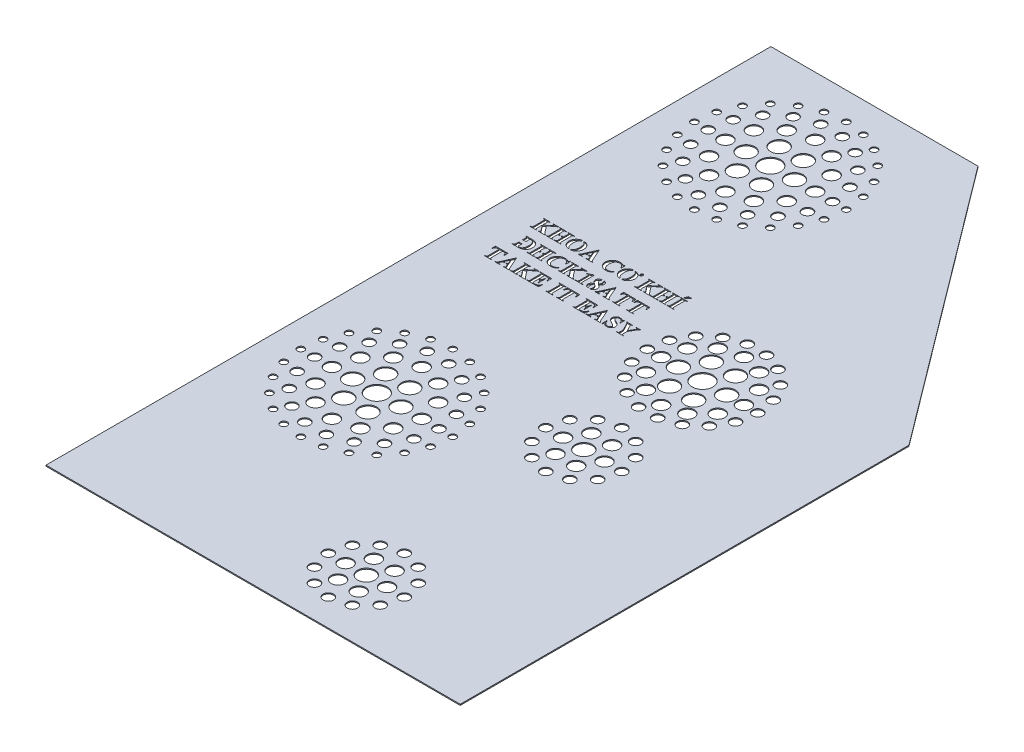
SolidWorks part; units mm, degrees
ref_plane "Front Plane" through (0, 0, 0) normal (0, 0, 1) x (1, 0, 0)
ref_plane "Top Plane" through (0, 0, 0) normal (0, 1, 0) x (1, 0, 0)
ref_plane "Right Plane" through (0, 0, 0) normal (1, 0, 0) x (0, 0, -1)
sketch "Sketch1" plane through (0, 0, 0) normal (0, 1, 0) x (1, 0, 0)
  line L0 (286.5, 0) -> (-313.5, 0)
  line L1 (-313.5, 0) -> (-313.5, 1050)
  line L2 (-313.5, 1050) -> (-13.5, 1050)
  line L3 (-13.5, 1050) -> (286.5, 650)
  line L4 (286.5, 650) -> (286.5, 0)
  line L5 (-263.5, 650) -> (-63.5, 650) construction
  circle A259 centre (91.5, 581) radius 12.5
  circle A260 centre (116.5, 581) radius 10
  circle A261 centre (136.5, 581) radius 7.5
  circle A263 centre (56.5, 581) radius 15
  circle A264 centre (74, 550.6891) radius 12.5
  circle A265 centre (39, 550.6891) radius 12.5
  circle A266 centre (21.5, 581) radius 12.5
  circle A267 centre (39, 611.3109) radius 12.5
  circle A268 centre (74, 611.3109) radius 12.5
  circle A269 centre (108.4615, 551) radius 10
  circle A270 centre (86.5, 529.0385) radius 10
  circle A271 centre (56.5, 521) radius 10
  circle A272 centre (26.5, 529.0385) radius 10
  circle A273 centre (4.5385, 551) radius 10
  circle A274 centre (-3.5, 581) radius 10
  circle A275 centre (4.5385, 611) radius 10
  circle A276 centre (26.5, 632.9615) radius 10
  circle A277 centre (56.5, 641) radius 10
  circle A278 centre (86.5, 632.9615) radius 10
  circle A279 centre (108.4615, 611) radius 10
  circle A280 centre (131.6754, 553.6384) radius 7.5
  circle A281 centre (117.7836, 529.577) radius 7.5
  circle A282 centre (96.5, 511.718) radius 7.5
  circle A283 centre (70.3919, 502.2154) radius 7.5
  circle A284 centre (42.6081, 502.2154) radius 7.5
  circle A285 centre (16.5, 511.718) radius 7.5
  circle A286 centre (-4.7836, 529.577) radius 7.5
  circle A287 centre (-18.6754, 553.6384) radius 7.5
  circle A288 centre (-23.5, 581) radius 7.5
  circle A289 centre (-18.6754, 608.3616) radius 7.5
  circle A290 centre (-4.7836, 632.423) radius 7.5
  circle A291 centre (16.5, 650.282) radius 7.5
  circle A292 centre (42.6081, 659.7846) radius 7.5
  circle A293 centre (70.3919, 659.7846) radius 7.5
  circle A294 centre (96.5, 650.282) radius 7.5
  circle A295 centre (117.7836, 632.423) radius 7.5
  circle A296 centre (131.6754, 608.3616) radius 7.5
  circle A362 centre (86.5, 409) radius 10
  circle A363 centre (111.5, 409) radius 7.5
  circle A364 centre (71.5, 383.0192) radius 10
  circle A365 centre (41.5, 383.0192) radius 10
  circle A366 centre (26.5, 409) radius 10
  circle A367 centre (41.5, 434.9808) radius 10
  circle A368 centre (71.5, 434.9808) radius 10
  circle A369 centre (104.1314, 381.5) radius 7.5
  circle A370 centre (84, 361.3686) radius 7.5
  circle A371 centre (56.5, 354) radius 7.5
  circle A372 centre (29, 361.3686) radius 7.5
  circle A373 centre (8.8686, 381.5) radius 7.5
  circle A374 centre (1.5, 409) radius 7.5
  circle A375 centre (8.8686, 436.5) radius 7.5
  circle A376 centre (29, 456.6314) radius 7.5
  circle A377 centre (56.5, 464) radius 7.5
  circle A378 centre (84, 456.6314) radius 7.5
  circle A379 centre (104.1314, 436.5) radius 7.5
  circle A380 centre (56.5, 409) radius 12.5
  circle A381 centre (86.5, 94) radius 10
  circle A382 centre (111.5, 94) radius 7.5
  circle A383 centre (71.5, 68.0192) radius 10
  circle A384 centre (41.5, 68.0192) radius 10
  circle A385 centre (26.5, 94) radius 10
  circle A386 centre (41.5, 119.9808) radius 10
  circle A387 centre (71.5, 119.9808) radius 10
  circle A388 centre (104.1314, 66.5) radius 7.5
  circle A389 centre (84, 46.3686) radius 7.5
  circle A390 centre (56.5, 39) radius 7.5
  circle A391 centre (29, 46.3686) radius 7.5
  circle A392 centre (8.8686, 66.5) radius 7.5
  circle A393 centre (1.5, 94) radius 7.5
  circle A394 centre (8.8686, 121.5) radius 7.5
  circle A395 centre (29, 141.6314) radius 7.5
  circle A396 centre (56.5, 149) radius 7.5
  circle A397 centre (84, 141.6314) radius 7.5
  circle A398 centre (104.1314, 121.5) radius 7.5
  circle A399 centre (56.5, 94) radius 12.5
  circle A400 centre (-164.5, 330.2) radius 15
  circle A401 centre (-129.5, 330.2) radius 12.5
  circle A402 centre (-99.5, 330.2) radius 10
  circle A403 centre (-74.5, 330.2) radius 7.5
  circle A404 centre (-54.5, 330.2) radius 5
  circle A407 centre (-147, 299.8891) radius 12.5
  circle A408 centre (-182, 299.8891) radius 12.5
  circle A409 centre (-199.5, 330.2) radius 12.5
  circle A410 centre (-182, 360.5109) radius 12.5
  circle A411 centre (-147, 360.5109) radius 12.5
  circle A412 centre (-108.2083, 297.7) radius 10
  circle A413 centre (-132, 273.9083) radius 10
  circle A414 centre (-164.5, 265.2) radius 10
  circle A415 centre (-197, 273.9083) radius 10
  circle A416 centre (-220.7917, 297.7) radius 10
  circle A417 centre (-229.5, 330.2) radius 10
  circle A418 centre (-220.7917, 362.7) radius 10
  circle A419 centre (-197, 386.4917) radius 10
  circle A420 centre (-164.5, 395.2) radius 10
  circle A421 centre (-132, 386.4917) radius 10
  circle A422 centre (-108.2083, 362.7) radius 10
  circle A423 centre (-79.9277, 299.4182) radius 7.5
  circle A424 centre (-95.556, 272.3491) radius 7.5
  circle A425 centre (-119.5, 252.2577) radius 7.5
  circle A426 centre (-148.8717, 241.5673) radius 7.5
  circle A427 centre (-180.1283, 241.5673) radius 7.5
  circle A428 centre (-209.5, 252.2577) radius 7.5
  circle A429 centre (-233.444, 272.3491) radius 7.5
  circle A430 centre (-249.0723, 299.4182) radius 7.5
  circle A431 centre (-254.5, 330.2) radius 7.5
  circle A432 centre (-249.0723, 360.9818) radius 7.5
  circle A433 centre (-233.444, 388.0509) radius 7.5
  circle A434 centre (-209.5, 408.1423) radius 7.5
  circle A435 centre (-180.1283, 418.8327) radius 7.5
  circle A436 centre (-148.8717, 418.8327) radius 7.5
  circle A437 centre (-119.5, 408.1423) radius 7.5
  circle A438 centre (-95.556, 388.0509) radius 7.5
  circle A439 centre (-79.9277, 360.9818) radius 7.5
  circle A440 centre (-58.2482, 301.7299) radius 5
  circle A441 centre (-69.2372, 275.2) radius 5
  circle A442 centre (-86.7183, 252.4183) radius 5
  circle A443 centre (-109.5, 234.9372) radius 5
  circle A444 centre (-136.0299, 223.9482) radius 5
  circle A445 centre (-164.5, 220.2) radius 5
  circle A446 centre (-192.9701, 223.9482) radius 5
  circle A447 centre (-219.5, 234.9372) radius 5
  circle A448 centre (-242.2817, 252.4183) radius 5
  circle A449 centre (-259.7628, 275.2) radius 5
  circle A450 centre (-270.7518, 301.7299) radius 5
  circle A451 centre (-274.5, 330.2) radius 5
  circle A452 centre (-270.7518, 358.6701) radius 5
  circle A453 centre (-259.7628, 385.2) radius 5
  circle A454 centre (-242.2817, 407.9817) radius 5
  circle A455 centre (-219.5, 425.4628) radius 5
  circle A456 centre (-192.9701, 436.4518) radius 5
  circle A457 centre (-164.5, 440.2) radius 5
  circle A458 centre (-136.0299, 436.4518) radius 5
  circle A459 centre (-109.5, 425.4628) radius 5
  circle A460 centre (-86.7183, 407.9817) radius 5
  circle A461 centre (-69.2372, 385.2) radius 5
  circle A462 centre (-58.2482, 358.6701) radius 5
  circle A463 centre (-164.5, 900.2) radius 15
  circle A464 centre (-129.5, 900.2) radius 12.5
  circle A465 centre (-99.5, 900.2) radius 10
  circle A466 centre (-74.5, 900.2) radius 7.5
  circle A467 centre (-54.5, 900.2) radius 5
  circle A468 centre (-147, 869.8891) radius 12.5
  circle A469 centre (-182, 869.8891) radius 12.5
  circle A470 centre (-199.5, 900.2) radius 12.5
  circle A471 centre (-182, 930.5109) radius 12.5
  circle A472 centre (-147, 930.5109) radius 12.5
  circle A473 centre (-108.2083, 867.7) radius 10
  circle A474 centre (-132, 843.9083) radius 10
  circle A475 centre (-164.5, 835.2) radius 10
  circle A476 centre (-197, 843.9083) radius 10
  circle A477 centre (-220.7917, 867.7) radius 10
  circle A478 centre (-229.5, 900.2) radius 10
  circle A479 centre (-220.7917, 932.7) radius 10
  circle A480 centre (-197, 956.4917) radius 10
  circle A481 centre (-164.5, 965.2) radius 10
  circle A482 centre (-132, 956.4917) radius 10
  circle A483 centre (-108.2083, 932.7) radius 10
  circle A484 centre (-79.9277, 869.4182) radius 7.5
  circle A485 centre (-95.556, 842.3491) radius 7.5
  circle A486 centre (-119.5, 822.2577) radius 7.5
  circle A487 centre (-148.8717, 811.5673) radius 7.5
  circle A488 centre (-180.1283, 811.5673) radius 7.5
  circle A489 centre (-209.5, 822.2577) radius 7.5
  circle A490 centre (-233.444, 842.3491) radius 7.5
  circle A491 centre (-249.0723, 869.4182) radius 7.5
  circle A492 centre (-254.5, 900.2) radius 7.5
  circle A493 centre (-249.0723, 930.9818) radius 7.5
  circle A494 centre (-233.444, 958.0509) radius 7.5
  circle A495 centre (-209.5, 978.1423) radius 7.5
  circle A496 centre (-180.1283, 988.8327) radius 7.5
  circle A497 centre (-148.8717, 988.8327) radius 7.5
  circle A498 centre (-119.5, 978.1423) radius 7.5
  circle A499 centre (-95.556, 958.0509) radius 7.5
  circle A500 centre (-79.9277, 930.9818) radius 7.5
  circle A501 centre (-58.2482, 871.7299) radius 5
  circle A502 centre (-69.2372, 845.2) radius 5
  circle A503 centre (-86.7183, 822.4183) radius 5
  circle A504 centre (-109.5, 804.9372) radius 5
  circle A505 centre (-136.0299, 793.9482) radius 5
  circle A506 centre (-164.5, 790.2) radius 5
  circle A507 centre (-192.9701, 793.9482) radius 5
  circle A508 centre (-219.5, 804.9372) radius 5
  circle A509 centre (-242.2817, 822.4183) radius 5
  circle A510 centre (-259.7628, 845.2) radius 5
  circle A511 centre (-270.7518, 871.7299) radius 5
  circle A512 centre (-274.5, 900.2) radius 5
  circle A513 centre (-270.7518, 928.6701) radius 5
  circle A514 centre (-259.7628, 955.2) radius 5
  circle A515 centre (-242.2817, 977.9817) radius 5
  circle A516 centre (-219.5, 995.4628) radius 5
  circle A517 centre (-192.9701, 1006.4518) radius 5
  circle A518 centre (-164.5, 1010.2) radius 5
  circle A519 centre (-136.0299, 1006.4518) radius 5
  circle A520 centre (-109.5, 995.4628) radius 5
  circle A521 centre (-86.7183, 977.9817) radius 5
  circle A522 centre (-69.2372, 955.2) radius 5
  circle A523 centre (-58.2482, 928.6701) radius 5
  text T0 "<b>KHOA CƠ KHÍ</b>\r\n<b>DHCK18ATT</b>\r\n<b>TAKE IT EASY</b>" font "Times New Roman" height 20
  point P32 (-164.5, 330.2)
  point P56 (-164.5, 330.2)
  point P90 (-164.5, 330.2)
  point P137 (-164.5, 330.2)
  point P156 (-164.5, 900.2)
  point P180 (-164.5, 900.2)
  point P214 (-164.5, 900.2)
  point P261 (-164.5, 900.2)
  point P550 (56.5, 581)
  point P574 (56.5, 581)
  point P609 (56.5, 581)
  point P656 (56.5, 581)
  point P672 (56.5, 409)
  point P695 (56.5, 409)
  point P710 (56.5, 94)
  point P733 (56.5, 94)
  dimension "D5" = 30
  dimension "D6" = 35
  dimension "D7" = 2
  dimension "D8" = 2
  dimension "D16" = 172
  dimension "D9" = 35
  dimension "D17" = 30
  dimension "D18" = 6
  dimension "D10" = 30
  dimension "D11" = 25
  dimension "D12" = 20
  dimension "D13" = 25
  dimension "D14" = 20
  dimension "D15" = 15
  dimension "D27" = 10
  dimension "D29" = 719.8
  dimension "D30" = 25
  dimension "D31" = 20
  dimension "D32" = 20
  dimension "D21" = 25
  dimension "D33" = 15
  dimension "D34" = 30
  dimension "D35" = 25
  dimension "D36" = 25
  dimension "D37" = 20
  dimension "D38" = 15
  dimension "D1" = 650
  dimension "D2" = 1050
  dimension "D3" = 600
  dimension "300" = 300
  dimension "D24" = 370
  dimension "D25" = 469
  dimension "D22" = 200
  dimension "D23" = 50
  dimension "D26" = 400
  dimension "D28" = 149
  dimension "D39" = 315
  dimension "D19" = 12
  dimension "D20" = 18
extrude "Boss-Extrude1" add sketch "Sketch1" along normal blind 1.5
sketch "Sketch2" plane through (0, 1.5, 0) normal (0, 1, 0) x (1, 0, 0)
  line L1 (-227.3073, 658.93) -> (-229.6927, 658.93)
  line L2 (-227.3073, 658.93) -> (-227.3073, 661.988)
  line L3 (-227.3073, 661.988) -> (-229.6927, 661.988)
  line L4 (-229.6927, 658.93) -> (-229.6927, 661.988)
  line L5 (-227.3073, 658.93) -> (-229.6927, 661.988) construction
  line L6 (-227.3073, 661.988) -> (-229.6927, 658.93) construction
  line L7 (-203.7646, 667.9852) -> (-206.7139, 667.9852)
  line L8 (-203.7646, 667.9852) -> (-203.7646, 671.1874)
  line L9 (-203.7646, 671.1874) -> (-206.7139, 671.1874)
  line L10 (-206.7139, 667.9852) -> (-206.7139, 671.1874)
  line L11 (-203.7646, 667.9852) -> (-206.7139, 671.1874) construction
  line L12 (-203.7646, 671.1874) -> (-206.7139, 667.9852) construction
  line L13 (-203.7646, 648.6458) -> (-206.7139, 648.6458)
  line L14 (-203.7646, 648.6458) -> (-203.7646, 652.0165)
  line L15 (-203.7646, 652.0165) -> (-206.7139, 652.0165)
  line L16 (-206.7139, 648.6458) -> (-206.7139, 652.0165)
  line L17 (-203.7646, 648.6458) -> (-206.7139, 652.0165) construction
  line L18 (-203.7646, 652.0165) -> (-206.7139, 648.6458) construction
  line L19 (-183.2916, 655.0807) -> (-185.2189, 655.0807)
  line L20 (-183.2916, 655.0807) -> (-183.2916, 657.4898)
  line L21 (-183.2916, 657.4898) -> (-185.2189, 657.4898)
  line L22 (-185.2189, 655.0807) -> (-185.2189, 657.4898)
  line L23 (-183.2916, 655.0807) -> (-185.2189, 657.4898) construction
  line L24 (-183.2916, 657.4898) -> (-185.2189, 655.0807) construction
  line L25 (-129.4086, 667.9852) -> (-132.6017, 667.9852)
  line L26 (-129.4086, 667.9852) -> (-129.4086, 671.1874)
  line L27 (-129.4086, 671.1874) -> (-132.6017, 671.1874)
  line L28 (-132.6017, 667.9852) -> (-132.6017, 671.1874)
  line L29 (-129.4086, 667.9852) -> (-132.6017, 671.1874) construction
  line L30 (-129.4086, 671.1874) -> (-132.6017, 667.9852) construction
  line L31 (-129.4086, 648.6458) -> (-132.6017, 648.6458)
  line L32 (-129.4086, 648.6458) -> (-129.4086, 652.0165)
  line L33 (-129.4086, 652.0165) -> (-132.6017, 652.0165)
  line L34 (-132.6017, 648.6458) -> (-132.6017, 652.0165)
  line L35 (-129.4086, 648.6458) -> (-132.6017, 652.0165) construction
  line L36 (-129.4086, 652.0165) -> (-132.6017, 648.6458) construction
  line L37 (-75.661, 658.93) -> (-78.0057, 658.93)
  line L38 (-75.661, 658.93) -> (-75.661, 661.988)
  line L39 (-75.661, 661.988) -> (-78.0057, 661.988)
  line L40 (-78.0057, 658.93) -> (-78.0057, 661.988)
  line L41 (-75.661, 658.93) -> (-78.0057, 661.988) construction
  line L42 (-75.661, 661.988) -> (-78.0057, 658.93) construction
  line L43 (-244.2793, 622.3115) -> (-253.7001, 622.3115)
  line L44 (-244.2793, 622.3115) -> (-244.2793, 627.9107)
  line L45 (-244.2793, 627.9107) -> (-253.7001, 627.9107)
  line L46 (-253.7001, 622.3115) -> (-253.7001, 627.9107)
  line L47 (-244.2793, 622.3115) -> (-253.7001, 627.9107) construction
  line L48 (-244.2793, 627.9107) -> (-253.7001, 622.3115) construction
  line L49 (-219.2306, 623.9207) -> (-222.7694, 623.9207)
  line L50 (-219.2306, 623.9207) -> (-219.2306, 627.4482)
  line L51 (-219.2306, 627.4482) -> (-222.7694, 627.4482)
  line L52 (-222.7694, 623.9207) -> (-222.7694, 627.4482)
  line L53 (-219.2306, 623.9207) -> (-222.7694, 627.4482) construction
  line L54 (-219.2306, 627.4482) -> (-222.7694, 623.9207) construction
  line L55 (-140.1148, 632.969) -> (-143.1266, 632.969)
  line L56 (-140.1148, 632.969) -> (-140.1148, 636.7397)
  line L57 (-140.1148, 636.7397) -> (-143.1266, 636.7397)
  line L58 (-143.1266, 632.969) -> (-143.1266, 636.7397)
  line L59 (-140.1148, 632.969) -> (-143.1266, 636.7397) construction
  line L60 (-140.1148, 636.7397) -> (-143.1266, 632.969) construction
  line L61 (-140.5431, 613.7711) -> (-143.6792, 613.7711)
  line L62 (-140.5431, 613.7711) -> (-140.5431, 617.4235)
  line L63 (-140.5431, 617.4235) -> (-143.6792, 617.4235)
  line L64 (-143.6792, 613.7711) -> (-143.6792, 617.4235)
  line L65 (-140.5431, 613.7711) -> (-143.6792, 617.4235) construction
  line L66 (-140.5431, 617.4235) -> (-143.6792, 613.7711) construction
  line L67 (-123.8878, 619.9311) -> (-126.2893, 619.9311)
  line L68 (-123.8878, 619.9311) -> (-123.8878, 622.8798)
  line L69 (-123.8878, 622.8798) -> (-126.2893, 622.8798)
  line L70 (-126.2893, 619.9311) -> (-126.2893, 622.8798)
  line L71 (-123.8878, 619.9311) -> (-126.2893, 622.8798) construction
  line L72 (-123.8878, 622.8798) -> (-126.2893, 619.9311) construction
  line L73 (-233.1289, 584.954) -> (-235.3815, 584.954)
  line L74 (-233.1289, 584.954) -> (-233.1289, 588.0837)
  line L75 (-233.1289, 588.0837) -> (-235.3815, 588.0837)
  line L76 (-235.3815, 584.954) -> (-235.3815, 588.0837)
  line L77 (-233.1289, 584.954) -> (-235.3815, 588.0837) construction
  line L78 (-233.1289, 588.0837) -> (-235.3815, 584.954) construction
  line L79 (-101.6547, 585.1955) -> (-103.5224, 585.1955)
  line L80 (-101.6547, 585.1955) -> (-101.6547, 587.8421)
  line L81 (-101.6547, 587.8421) -> (-103.5224, 587.8421)
  line L82 (-103.5224, 585.1955) -> (-103.5224, 587.8421)
  line L83 (-101.6547, 585.1955) -> (-103.5224, 587.8421) construction
  line L84 (-101.6547, 587.8421) -> (-103.5224, 585.1955) construction
  point P0 (-228.5, 660.459)
  point P5 (-205.2393, 669.5863)
  point P10 (-205.2393, 650.3311)
  point P15 (-184.2552, 656.2852)
  point P20 (-131.0051, 669.5863)
  point P25 (-131.0051, 650.3311)
  point P30 (-76.8333, 660.459)
  point P35 (-248.9897, 625.1111)
  point P40 (-221, 625.6845)
  point P45 (-141.6207, 634.8544)
  point P50 (-142.1111, 615.5973)
  point P55 (-125.0885, 621.4055)
  point P60 (-234.2552, 586.5188)
  point P65 (-102.5885, 586.5188)
extrude "Boss-Extrude2" add sketch "Sketch2" against normal blind 1.5
